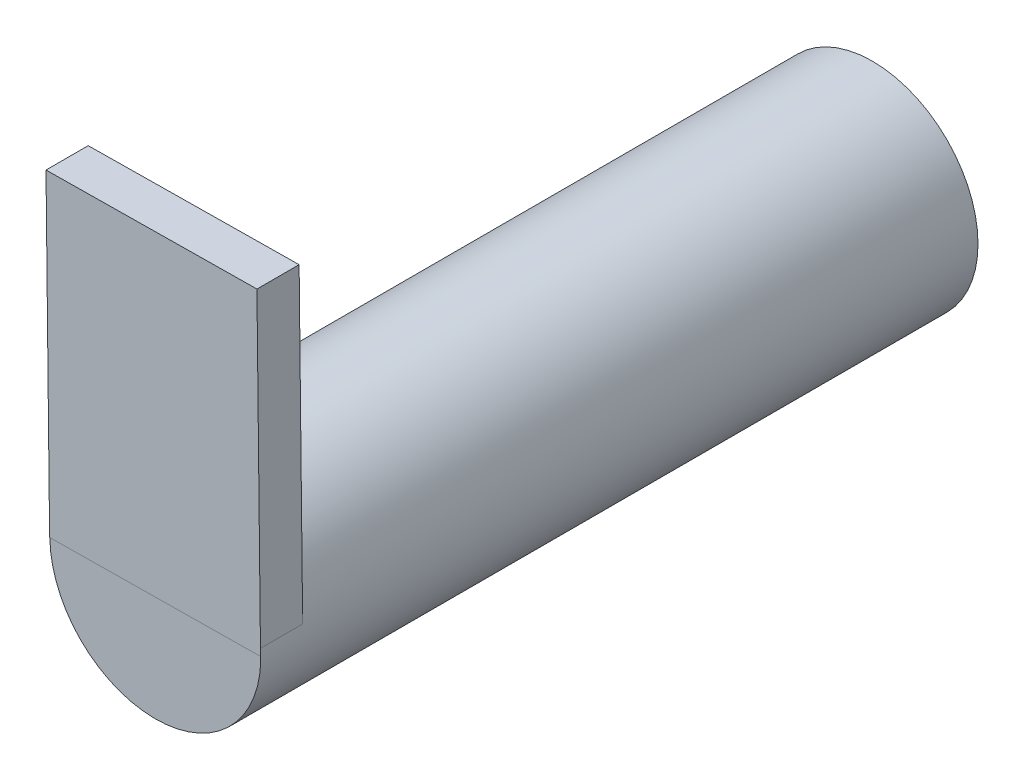
SolidWorks part; units mm, degrees
ref_plane "Front Plane" through (0, 0, 0) normal (0, 0, 1) x (1, 0, 0)
ref_plane "Top Plane" through (0, 0, 0) normal (0, 1, 0) x (1, 0, 0)
ref_plane "Right Plane" through (0, 0, 0) normal (1, 0, 0) x (0, 0, -1)
sketch "Sketch1" plane through (0, 0, 0) normal (0, 0, 1) x (1, 0, 0)
  circle A0 centre (-14.9361, 10.2178) radius 5
extrude "Boss-Extrude1" add sketch "Sketch1" along normal blind 34
ref_axis "Axis1" through (-14.9361, 10.2178, 34) along (0, 0, -1)
ref_plane "Plane1" through (-0.1185, 10.387, 0) normal (-0.0114, 0.9999, 0) x (0.9999, 0.0114, 0)
sketch "Sketch3" plane through (-0.1185, 10.387, 0) normal (-0.0114, 0.9999, 0) x (0.9999, 0.0114, 0)
  line L3 (-19.8294, -34) -> (-9.8294, -34)
  line L4 (-19.8294, -34) -> (-19.8294, -32)
  line L7 (-19.8294, -32) -> (-9.8294, -32)
  line L8 (-9.8294, -34) -> (-9.8294, -32)
extrude "Boss-Extrude2" add sketch "Sketch3" along normal blind 15
